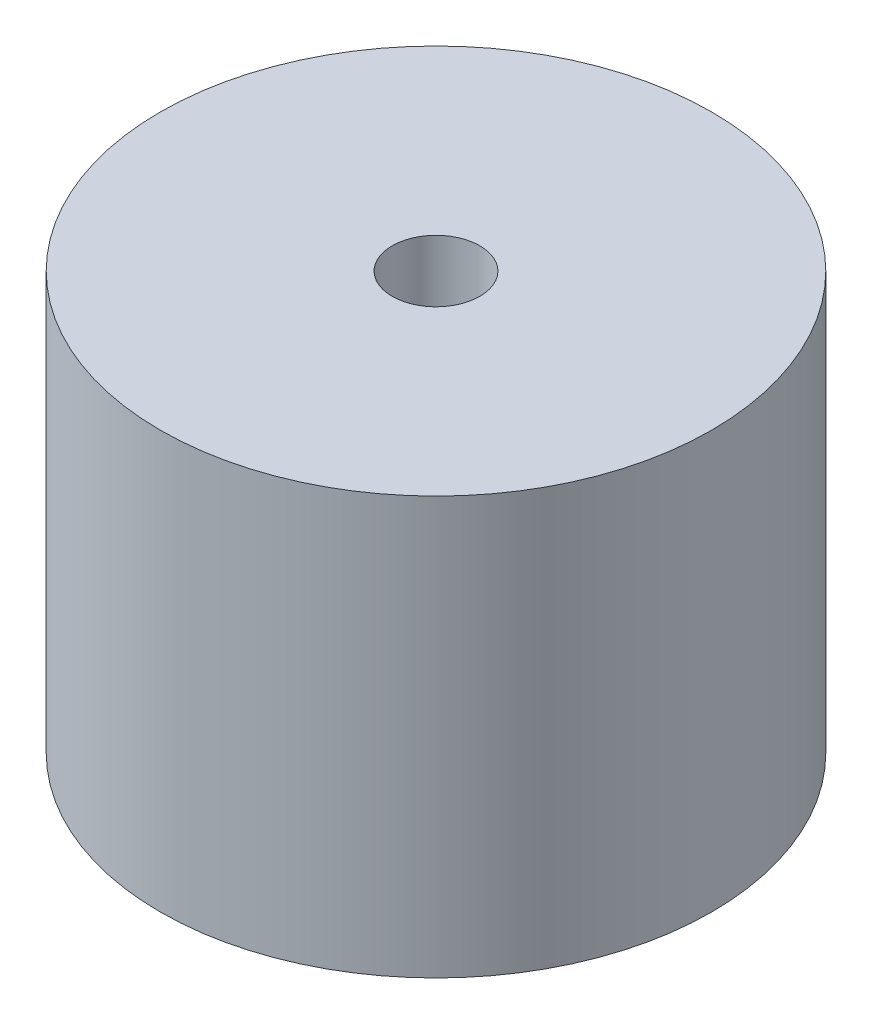
SolidWorks part; units mm, degrees
ref_plane "Front Plane" through (0, 0, 0) normal (0, 0, 1) x (1, 0, 0)
ref_plane "Top Plane" through (0, 0, 0) normal (0, 1, 0) x (1, 0, 0)
ref_plane "Right Plane" through (0, 0, 0) normal (1, 0, 0) x (0, 0, -1)
sketch "Sketch1" plane through (0, 0, 0) normal (0, 1, 0) x (1, 0, 0)
  circle A0 centre (0, 0) radius 2.1
  circle A1 centre (0, 0) radius 13.21
  dimension "D1" = 4.2
  dimension "D2" = 13.21
extrude "Boss-Extrude1" add sketch "Sketch1" along normal blind 20
sketch "Sketch2" plane through (0, 0, 0) normal (1, 0, 0) x (0, 0, -1)
  line L0 (-13.21, 0) -> (-13.21, -12.2)
  line L1 (-13.21, -12.2) -> (-4.21, -12.2)
  line L2 (-4.21, -12.2) -> (-4.21, 0)
  line L3 (-4.21, 0) -> (-13.21, 0)
  line L4 (-13.21, 0) -> (13.21, 0) construction
  circle A0 centre (-10.21, -8.2) radius 1.2 construction
  point P9 (-13.21, -11.6164)
  dimension "D1" = 4
  dimension "D2" = 9
